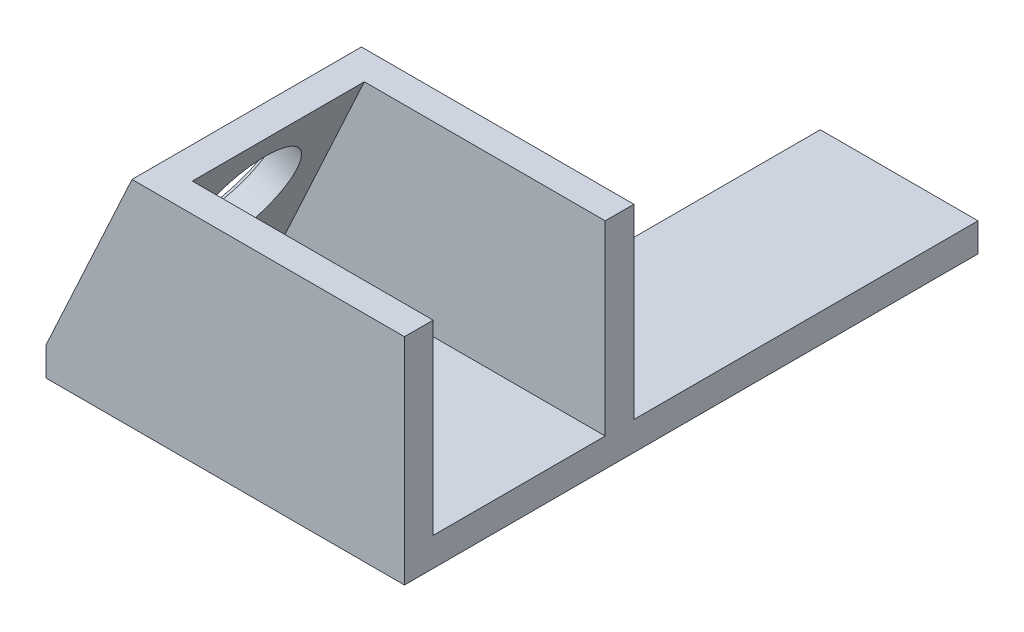
SolidWorks part; units mm, degrees
ref_plane "Front Plane" through (0, 0, 0) normal (0, 0, 1) x (1, 0, 0)
ref_plane "Top Plane" through (0, 0, 0) normal (0, 1, 0) x (1, 0, 0)
ref_plane "Right Plane" through (0, 0, 0) normal (1, 0, 0) x (0, 0, -1)
sketch "Sketch1" plane through (0, 0, 0) normal (0, 1, 0) x (1, 0, 0)
  line L1 (-27.5, -50) -> (27.5, -50)
  line L2 (-27.5, -50) -> (-27.5, 50)
  line L3 (-27.5, 50) -> (27.5, 50)
  line L4 (27.5, -50) -> (27.5, 50)
  line L5 (-27.5, -50) -> (27.5, 50) construction
  line L6 (-27.5, 50) -> (27.5, -50) construction
  line L7 (-27.5, -50) -> (27.5, -50)
  line L8 (-27.5, -50) -> (-27.5, -70)
  line L9 (-27.5, -70) -> (27.5, -70)
  line L10 (27.5, -50) -> (27.5, -70)
  line L11 (27.5, -70) -> (-27.5, -70)
  line L12 (27.5, -70) -> (27.5, -150)
  line L13 (27.5, -150) -> (-27.5, -150)
  line L14 (-27.5, -70) -> (-27.5, -150)
  line L15 (-27.5, -70) -> (-97.5, -70)
  line L16 (-27.5, -70) -> (-27.5, -150)
  line L17 (-27.5, -150) -> (-97.5, -150)
  line L18 (-97.5, -70) -> (-97.5, -150)
  point P0 (0, 0)
  dimension "D1" = 100
  dimension "D2" = 55
  dimension "D3" = 20
  dimension "D4" = 80
  dimension "D5" = 70
extrude "Boss-Extrude1" add sketch "Sketch1" along normal blind 10 contours L18 L8 | L10 L1 L8 L9 | L1 L4 L3 L2 | L9 L14 L13 L12 region at (0, 0, 0) region at (0, 0, 60) region at (0, 0, 110) region at (-62.5, 0, 110)
sketch "Sketch4" plane through (0, 0, 150) normal (0, 0, 1) x (1, 0, 0)
  line L0 (27.5, 10) -> (27.5, 75)
  line L5 (27.5, 10) -> (-97.5, 10) construction
  line L6 (27.5, 75) -> (-67.5, 75)
  line L7 (27.5, 75) -> (27.5, 10)
  line L8 (27.5, 10) -> (-67.5, 10)
  line L9 (-67.5, 75) -> (-67.5, 10)
  line L10 (-97.5, 10) -> (-67.5, 75)
  line L11 (-97.5, 10) -> (-67.5, 10)
  line M8 (27.5, 10) -> (-97.5, 10)
  dimension "D1" = 95
  dimension "D2" = 65
extrude "Boss-Extrude3" add sketch "Sketch4" against normal up to surface (80 mm away) contours L10 L9 M8 | L6 L9 L0 M8 region at (-20, 42.5, 150) region at (-77.5, 31.6667, 150) up to face at (-62.5, 5, 70)
shell "Shell1" thickness 10 removed face at (-20, 75, 110) removed face at (27.5, 28.3333, 56.6667)
sketch "Sketch5" plane through (-84.1829, 38.8537, 0) normal (-0.908, 0.4191, 0) x (0, 0, 1)
  line L0 (110, -31.7786) -> (110, -16.7786)
  line L1 (70, -31.7786) -> (150, -31.7786) construction
  line L2 (92.5, -16.7786) -> (127.5, -16.7786)
  line L3 (110, 39.8105) -> (110, 14.8105)
  line L4 (70, 39.8105) -> (150, 39.8105) construction
  circle A0 centre (127.5, -16.7786) radius 4.95
  circle A1 centre (92.5, -16.7786) radius 4.95
  circle A2 centre (110, -16.7786) radius 4.95
  circle A3 centre (92.5, -16.7786) radius 6.4
  circle A4 centre (110, -16.7786) radius 6.4
  circle A5 centre (127.5, -16.7786) radius 6.4
  circle A6 centre (110, 14.8105) radius 18.92
  point P7 (110, -16.7786)
  point P18 (127.5, -19.3415)
  dimension "D1" = 15
  dimension "D3" = 35
  dimension "D2" = 25
extrude "Cut-Extrude1" cut sketch "Sketch5" against normal up to surface (10 mm away) contours A1 | A2 | A0 | A6 up to face at (-71.4863, 42.5, 110)
chamfer "Chamfer1" distance 1 angle 45 1 edges at (-85.905, 35.1224, 110)
